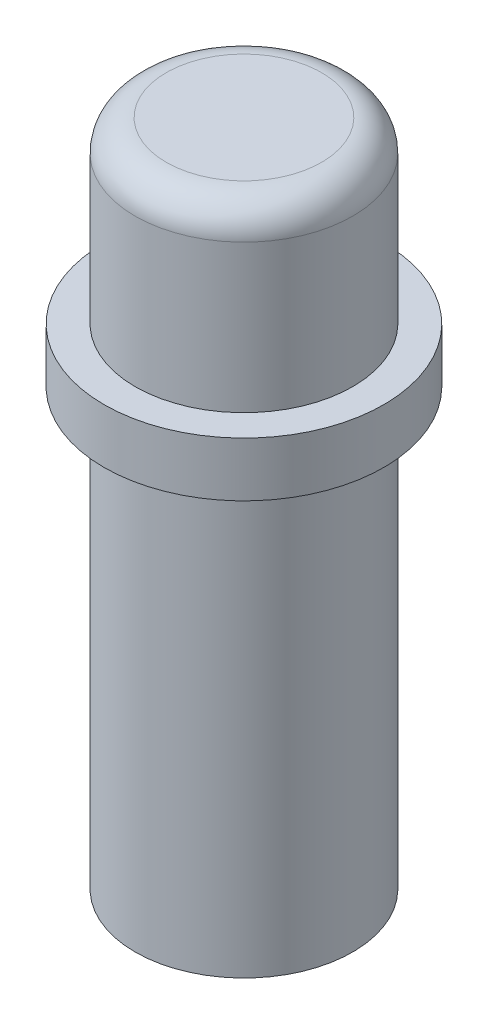
SolidWorks part; units mm, degrees
ref_plane "Front Plane" through (0, 0, 0) normal (0, 0, 1) x (1, 0, 0)
ref_plane "Top Plane" through (0, 0, 0) normal (0, 1, 0) x (1, 0, 0)
ref_plane "Right Plane" through (0, 0, 0) normal (1, 0, 0) x (0, 0, -1)
sketch "Sketch1" plane through (0, 0, 0) normal (0, 1, 0) x (1, 0, 0)
  circle A0 centre (0, 0) radius 3.5
  circle A1 centre (0, 0) radius 4.5
  dimension "D1" = 7
  dimension "D2" = 9
extrude "Boss-Extrude1" add sketch "Sketch1" along normal blind 14 contours A0 region at (0, 0, 0)
extrude "Boss-Extrude2" add sketch "Sketch1<4>" along normal blind 1.75 from surface contours A1 starting at face at (0, 14, 3.5)
sketch "Sketch1<4>" plane through (0, 0, 0) normal (0, 1, 0) x (1, 0, 0) same geometry as "Sketch1"
extrude "Boss-Extrude3" add sketch "Sketch1<5>" along normal blind 5.75 from surface contours A0 starting at face at (0, 15.75, 4.5)
sketch "Sketch1<5>" plane through (0, 0, 0) normal (0, 1, 0) x (1, 0, 0) same geometry as "Sketch1"
fillet "Fillet1" radius 1 1 edges at (0, 21.5, 3.5)
sketch "Sketch2" plane through (0, 0, 0) normal (0, -1, 0) x (1, 0, 0)
  circle A0 centre (0, 0) radius 2
  dimension "D1" = 4
extrude "Cut-Extrude1" cut sketch "Sketch2" against normal blind 0.5
equation "\"T\"= 1.75"
equation "\"D1@Boss-Extrude2\"=\"T\""
equation "\"D1@Boss-Extrude3\"=\"T\"+4"
